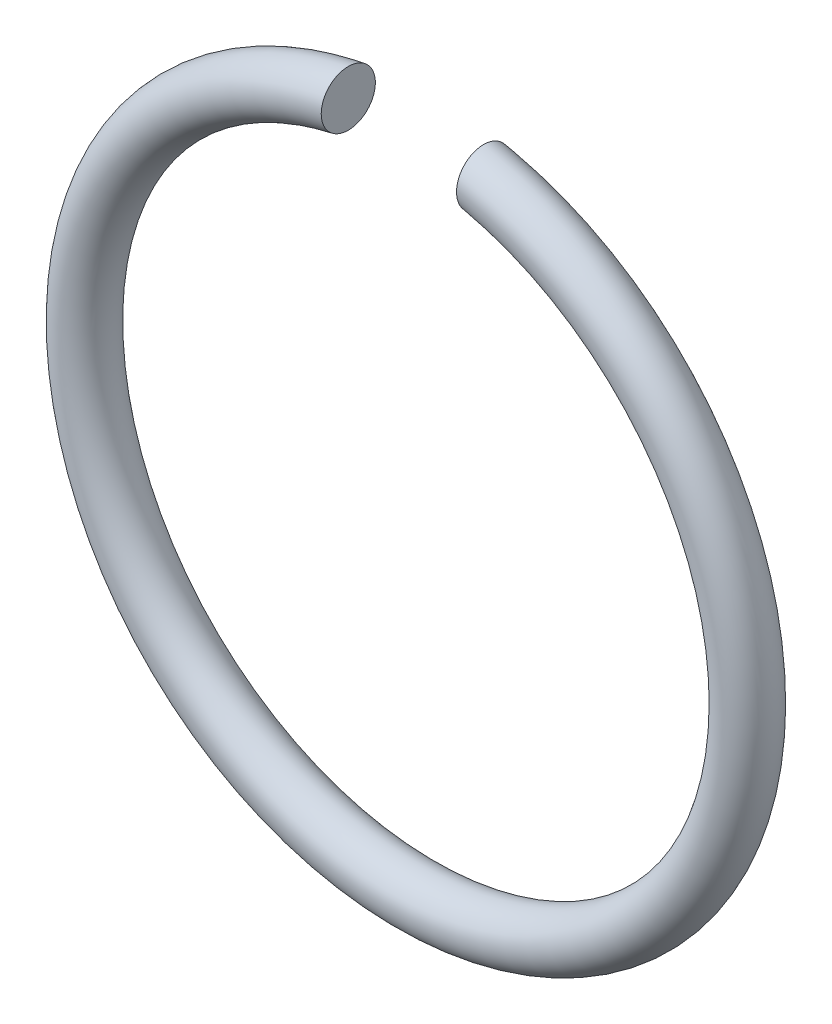
SolidWorks part; units mm, degrees
ref_plane "Front" through (0, 0, 0) normal (0, 0, 1) x (1, 0, 0)
ref_plane "Top" through (0, 0, 0) normal (0, 1, 0) x (1, 0, 0)
ref_plane "Right" through (0, 0, 0) normal (1, 0, 0) x (0, 0, -1)
sketch "Sketch1" plane through (0, 0, 0) normal (0, 0, 1) x (1, 0, 0)
  circle A1 centre (0, 0) radius 4.9
  dimension "D1" = 9.8
sketch "Sketch2" plane through (0, 0, 0) normal (0, 1, 0) x (1, 0, 0)
  circle A0 centre (4.9, 0) radius 0.4
  dimension "d1" = 0.8
sweep "Base-Sweep" add profiles "Sketch2" path "Sketch1"
sketch "Sketch3" plane through (0, 0, 0) normal (0, 0, 1) x (1, 0, 0)
  line L1 (-1, 0) -> (1, 0)
  line L2 (-1, 0) -> (-1, 5.3)
  line L3 (-1, 5.3) -> (1, 5.3)
  line L4 (1, 0) -> (1, 5.3)
  dimension "B/2" = 1
  dimension "D3" = 5.3
extrude "Cut-Extrude1" cut sketch "Sketch3" against normal through all and the other way through all
ref_axis "基准轴1" through (0, 0, 50) along (0, 0, -1)
equation "\"B/2@Sketch3\" = \"B@Sketch3\" / 2"
